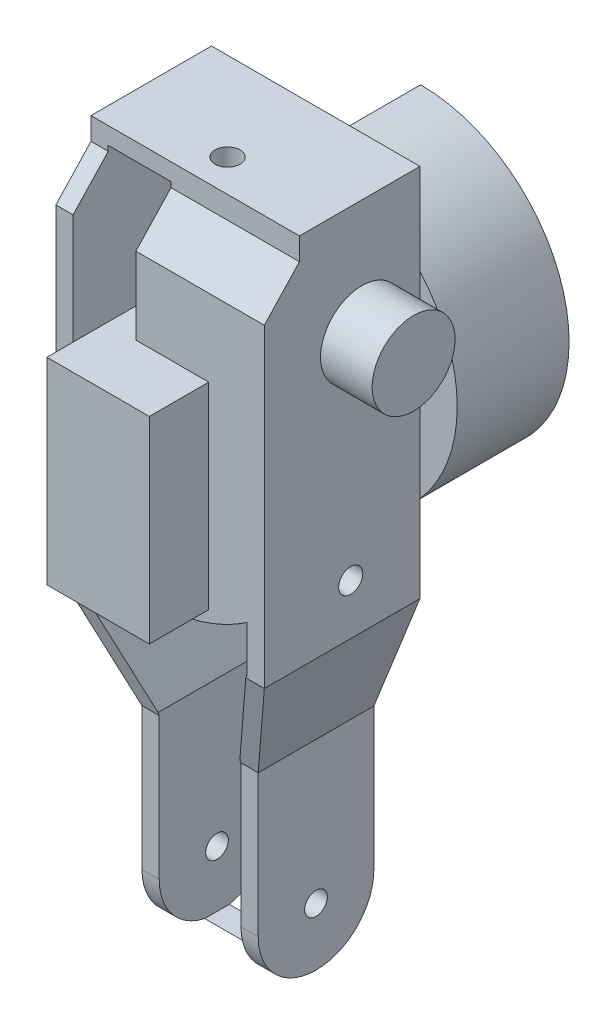
SolidWorks part; units mm, degrees
ref_plane "前视基准面" through (0, 0, 0) normal (0, 0, 1) x (1, 0, 0)
ref_plane "上视基准面" through (0, 0, 0) normal (0, 1, 0) x (1, 0, 0)
ref_plane "右视基准面" through (0, 0, 0) normal (1, 0, 0) x (0, 0, -1)
other "Configuration Table"
sketch "草图1" plane through (0, 0, 0) normal (1, 0, 0) x (0, 0, -1)
  line L0 (-9.04, -3.4) -> (-4.39, -16.885)
  line L1 (-9.04, -40.1) -> (9.04, -40.1)
  line L2 (-9.04, -40.1) -> (-9.04, 40.1)
  line L3 (-9.04, 40.1) -> (9.04, 40.1)
  line L4 (9.04, -40.1) -> (9.04, 40.1)
  line L5 (-9.04, -40.1) -> (9.04, 40.1) construction
  line L6 (-9.04, 40.1) -> (9.04, -40.1) construction
  line L7 (9.04, -33.385) -> (-4.39, -33.385)
  line L8 (9.04, -33.385) -> (9.04, -16.885)
  line L9 (9.04, -16.885) -> (-4.39, -16.885)
  line L10 (-4.39, -33.385) -> (-4.39, -16.885)
  line L11 (-9.04, 40.1) -> (9.04, 40.1)
  line L12 (-9.04, 40.1) -> (-9.04, -3.4)
  line L13 (-9.04, -3.4) -> (9.04, -3.4)
  line L14 (9.04, 40.1) -> (9.04, -3.4)
  line L15 (-4.96, 37.5) -> (-9.04, 33.15)
  line L16 (9.04, 40.1) -> (-4.96, 40.1)
  line L17 (9.04, 40.1) -> (9.04, 37.5)
  line L18 (9.04, 37.5) -> (-4.96, 37.5)
  line L19 (-4.96, 40.1) -> (-4.96, 37.5)
  line L20 (-4.96, 37.5) -> (-9.04, 37.5)
  line L21 (-4.96, 37.5) -> (-4.96, 33.15)
  line L22 (-4.96, 33.15) -> (-9.04, 33.15)
  line L23 (-9.04, 37.5) -> (-9.04, 33.15)
  circle A0 centre (2.325, -33.385) radius 6.715
  point P0 (0, 0)
  dimension "D1" = 18.08
  dimension "D2" = 80.2
  dimension "D3" = 13.43
  dimension "D4" = 16.5
  dimension "D5" = 43.5
  dimension "D6" = 14
  dimension "D7" = 2.6
  dimension "D8" = 4.35
extrude "凸台-拉伸1" add sketch "草图1" along normal blind 24.22 contours L11 L19 L18 L14 | L21 L22 L2 L13 L4 L18 | L22 L21 L15 | L13 L0 L9 L4 | A0 L4 L9 L10 | L7 A0 | L7 A0 region at (0, -9.8108, -1.1053) region at (0, 16.6006, -0.1721) region at (0, -22.5981, -2.325) region at (0, 34.6, 6.32) region at (0, -30.5351, -2.325) region at (0, -36.2349, -2.325) region at (0, 38.8, -2.04)
sketch "草图2" plane through (24.22, 0, 0) normal (1, 0, 0) x (0, 0, -1)
  line L0 (9.04, -16.885) -> (-4.39, -16.885) construction
  line L1 (9.04, -16.885) -> (-4.39, -16.885)
  line L7 (9.04, 40.1) -> (-4.96, 40.1)
  line L8 (-4.96, 40.1) -> (-4.96, 37.5)
  line L9 (-4.96, 37.5) -> (-9.04, 33.15)
  line L10 (-9.04, 33.15) -> (-9.04, -3.4)
  line L11 (-9.04, -3.4) -> (-4.39, -16.885)
  line L12 (-4.39, -16.885) -> (-4.39, -33.385)
  line L13 (9.04, -33.385) -> (9.04, 40.1)
  line L14 (9.04, 40.1) -> (-4.96, 40.1)
  line L15 (-4.96, 40.1) -> (-4.96, 37.5)
  line L16 (-4.96, 37.5) -> (-9.04, 33.15)
  line L17 (-9.04, 33.15) -> (-9.04, -3.4)
  line L18 (-9.04, -3.4) -> (-4.39, -16.885)
  line L19 (-4.39, -16.885) -> (-4.39, -33.385)
  line L20 (9.04, -33.385) -> (9.04, 40.1)
  arc A1 (-4.39, -33.385) -> (9.04, -33.385) centre (2.325, -33.385) ccw
  arc A2 (-4.39, -33.385) -> (9.04, -33.385) centre (2.325, -33.385) ccw
  line M14 (-4.39, -16.885) -> (-4.39, -33.385)
  arc M15 (-4.39, -33.385) -> (9.04, -33.385) centre (2.325, -33.385) ccw
  line M16 (9.04, -33.385) -> (9.04, 40.1)
  dimension "D1" = 0
extrude "切除-拉伸1" cut sketch "草图2" against normal blind 5.36 contours L1 M16 M14 M15 region at (24.22, -27.8236, -2.325)
sketch "草图3" plane through (0, 0, 0) normal (-1, 0, 0) x (0, 0, 1)
  line L0 (-9.04, -16.885) -> (4.39, -16.885) construction
  line L1 (-9.04, -16.885) -> (4.39, -16.885)
  line L7 (4.96, 40.1) -> (-9.04, 40.1)
  line L8 (-9.04, 40.1) -> (-9.04, -33.385)
  line L9 (4.39, -33.385) -> (4.39, -16.885)
  line L10 (4.39, -16.885) -> (9.04, -3.4)
  line L11 (9.04, -3.4) -> (9.04, 33.15)
  line L12 (9.04, 33.15) -> (4.96, 37.5)
  line L13 (4.96, 37.5) -> (4.96, 40.1)
  line L14 (4.96, 40.1) -> (-9.04, 40.1)
  line L15 (-9.04, 40.1) -> (-9.04, -33.385)
  line L16 (4.39, -33.385) -> (4.39, -16.885)
  line L17 (4.39, -16.885) -> (9.04, -3.4)
  line L18 (9.04, -3.4) -> (9.04, 33.15)
  line L19 (9.04, 33.15) -> (4.96, 37.5)
  line L20 (4.96, 37.5) -> (4.96, 40.1)
  arc A1 (-9.04, -33.385) -> (4.39, -33.385) centre (-2.325, -33.385) ccw
  arc A2 (-9.04, -33.385) -> (4.39, -33.385) centre (-2.325, -33.385) ccw
  line M10 (-9.04, 40.1) -> (-9.04, -33.385)
  arc M11 (-9.04, -33.385) -> (4.39, -33.385) centre (-2.325, -33.385) ccw
  line M12 (4.39, -33.385) -> (4.39, -16.885)
  dimension "D1" = 0
extrude "切除-拉伸2" cut sketch "草图3" against normal blind 5.36 contours L1 M10 M11 M12 region at (0, -27.8236, -2.325)
sketch "草图4" plane through (0, 0, -9.04) normal (0, 0, -1) x (-1, 0, 0)
  line L0 (0, -3.4) -> (-5.36, -16.885)
  line L1 (0, -3.4) -> (-24.22, -3.4)
  line L2 (-24.22, -3.4) -> (-18.86, -16.885)
  line L8 (-5.36, -16.885) -> (0, -16.885)
  line L9 (0, -16.885) -> (0, 40.1)
  line L10 (0, 40.1) -> (-24.22, 40.1)
  line L11 (-24.22, 40.1) -> (-24.22, -16.885)
  line L12 (-24.22, -16.885) -> (-18.86, -16.885)
  line L13 (-18.86, -16.885) -> (-18.86, -33.385)
  line L14 (-18.86, -33.385) -> (-5.36, -33.385)
  line L15 (-5.36, -33.385) -> (-5.36, -16.885)
  line L16 (-5.36, -16.885) -> (0, -16.885)
  line L17 (0, -16.885) -> (0, 40.1)
  line L18 (0, 40.1) -> (-24.22, 40.1)
  line L19 (-24.22, 40.1) -> (-24.22, -16.885)
  line L20 (-24.22, -16.885) -> (-18.86, -16.885)
  line L21 (-18.86, -16.885) -> (-18.86, -33.385)
  line L22 (-18.86, -33.385) -> (-5.36, -33.385)
  line L23 (-5.36, -33.385) -> (-5.36, -16.885)
  line M9 (-5.36, -16.885) -> (0, -16.885)
  line M10 (0, -16.885) -> (0, 40.1)
  line M12 (-24.22, 40.1) -> (-24.22, -16.885)
  line M13 (-24.22, -16.885) -> (-18.86, -16.885)
  dimension "D1" = 0
extrude "切除-拉伸3" cut sketch "草图4" against normal through all contours L2 M12 M13 | L0 M10 M9 region at (1.7867, -12.39, -9.04) region at (22.4333, -12.39, -9.04)
sketch "草图6" plane through (24.22, 0, 0) normal (1, 0, 0) x (0, 0, -1)
  line L0 (2.305, 31.47) -> (2.305, 40.1)
  line L1 (-9.04, 40.1) -> (9.04, 40.1) construction
  line L2 (-2.51, 26.655) -> (-9.04, 26.655)
  line L3 (-9.04, -40.1) -> (-9.04, 40.1) construction
  circle A0 centre (2.305, 26.655) radius 4.815
  line M6 (9.04, 40.1) -> (-4.96, 40.1)
  dimension "D3" = 9.63
  dimension "D1" = 6.53
  dimension "D2" = 8.63
extrude "凸台-拉伸3" add sketch "草图6" along normal blind 6 contours A0 M6 region at (24.22, 26.655, -2.305)
sketch "草图8" plane through (0, 0, -9.04) normal (0, 0, -1) x (-1, 0, 0)
  line L0 (-11.3, 18.1) -> (-11.3, 40.1)
  line L1 (-11.3, 18.1) -> (0, 18.1)
  line L2 (-11.3, 35.35) -> (-11.3, 0.85)
  line L8 (-24.22, -3.4) -> (-18.86, -16.885)
  line L9 (-18.86, -16.885) -> (-18.86, -33.385)
  line L10 (-18.86, -33.385) -> (-5.36, -33.385)
  line L11 (-5.36, -33.385) -> (-5.36, -16.885)
  line L12 (-5.36, -16.885) -> (0, -3.4)
  line L13 (0, -3.4) -> (0, 40.1)
  line L14 (0, 40.1) -> (-24.22, 40.1)
  line L15 (-24.22, 40.1) -> (-24.22, -3.4)
  line L16 (-24.22, -3.4) -> (-18.86, -16.885)
  line L17 (-18.86, -16.885) -> (-18.86, -33.385)
  line L18 (-18.86, -33.385) -> (-5.36, -33.385)
  line L19 (-5.36, -33.385) -> (-5.36, -16.885)
  line L20 (-5.36, -16.885) -> (0, -3.4)
  line L21 (0, -3.4) -> (0, 40.1)
  line L22 (0, 40.1) -> (-24.22, 40.1)
  line L23 (-24.22, 40.1) -> (-24.22, -3.4)
  circle A0 centre (-11.3, 18.1) radius 17.25
  dimension "D2" = 34.5
  dimension "D3" = 22
  dimension "D4" = 11.3
  dimension "D1" = 0
extrude "凸台-拉伸4" add sketch "草图8" along normal blind 13 contours L0 A0 L23 L2 | L23 A0 region at (17.373, 18.1, -9.04) region at (25.9721, 18.1, -9.04)
sketch "草图10" plane through (0, 0, 9.04) normal (0, 0, 1) x (1, 0, 0)
  line L0 (5.86, 24.2) -> (5.86, 40.1)
  line L1 (5.86, 24.2) -> (17.76, 24.2)
  line L2 (5.86, 24.2) -> (5.86, 1.3)
  line L3 (5.86, 1.3) -> (17.76, 1.3)
  line L4 (0, 33.15) -> (0, -3.4)
  line L5 (0, -3.4) -> (24.22, -3.4)
  line L6 (24.22, -3.4) -> (24.22, 33.15)
  line L7 (24.22, 33.15) -> (0, 33.15)
  line L8 (0, 33.15) -> (0, -3.4)
  line L9 (0, -3.4) -> (24.22, -3.4)
  line L10 (24.22, -3.4) -> (24.22, 33.15)
  line L11 (24.22, 33.15) -> (0, 33.15)
  line L12 (17.76, 24.2) -> (17.76, 1.3)
  line L13 (5.86, 24.2) -> (0, 24.2)
  line L18 (0, 37.5) -> (0, 33.15)
  line L19 (0, 33.15) -> (24.22, 33.15)
  line L20 (24.22, 33.15) -> (24.22, 37.5)
  line L21 (24.22, 37.5) -> (0, 37.5)
  line L22 (0, 37.5) -> (0, 33.15)
  line L23 (0, 33.15) -> (24.22, 33.15)
  line L24 (24.22, 33.15) -> (24.22, 37.5)
  line L25 (24.22, 37.5) -> (0, 37.5)
  line L26 (0, 40.1) -> (0, 37.5)
  line L27 (0, 37.5) -> (24.22, 37.5)
  line L28 (24.22, 37.5) -> (24.22, 40.1)
  line L29 (24.22, 40.1) -> (0, 40.1)
  line L30 (0, 40.1) -> (0, 37.5)
  line L31 (0, 37.5) -> (24.22, 37.5)
  line L32 (24.22, 37.5) -> (24.22, 40.1)
  line L33 (24.22, 40.1) -> (0, 40.1)
  dimension "D2" = 11.9
  dimension "D3" = 22.9
  dimension "D4" = 15.9
  dimension "D5" = 5.86
  dimension "D1" = 0
  dimension "D6" = 0
  dimension "D7" = 0
extrude "凸台-拉伸5" add sketch "草图10" along normal blind 6.9 contours L12 L1 L2 L3 region at (11.81, 12.75, 9.04)
sketch "草图11" plane through (0, 0, -9.04) normal (0, 0, -1) x (-1, 0, 0)
  line L4 (-22.22, -3.0171) -> (-16.86, -16.5021)
  line L5 (-16.86, -16.5021) -> (-16.86, -31.385)
  line L6 (-16.86, -31.385) -> (-7.36, -31.385)
  line L7 (-7.36, -31.385) -> (-7.36, -16.5021)
  line L8 (-7.36, -16.5021) -> (-2, -3.0171)
  line L9 (-2, -3.0171) -> (-2, 38.1)
  line L10 (-24.22, 6.6704) -> (-24.22, -3.4)
  line L11 (-24.22, -3.4) -> (-18.86, -16.885)
  line L12 (-18.86, -16.885) -> (-18.86, -33.385)
  line L13 (-18.86, -33.385) -> (-5.36, -33.385)
  line L14 (-5.36, -33.385) -> (-5.36, -16.885)
  line L15 (-5.36, -16.885) -> (0, -3.4)
  line L16 (0, -3.4) -> (0, 40.1)
  line L17 (0, 40.1) -> (-24.22, 40.1)
  line L18 (-24.22, 40.1) -> (-24.22, 29.5296)
  line L19 (-11.3, 35.35) -> (-11.3, 0.85)
  line L20 (-24.22, 6.6704) -> (-24.22, -3.4)
  line L21 (-24.22, -3.4) -> (-18.86, -16.885)
  line L22 (-18.86, -16.885) -> (-18.86, -33.385)
  line L23 (-18.86, -33.385) -> (-5.36, -33.385)
  line L24 (-5.36, -33.385) -> (-5.36, -16.885)
  line L25 (-5.36, -16.885) -> (0, -3.4)
  line L26 (0, -3.4) -> (0, 40.1)
  line L27 (0, 40.1) -> (-24.22, 40.1)
  line L28 (-24.22, 40.1) -> (-24.22, 29.5296)
  line L29 (-11.3, 35.35) -> (-11.3, 0.85)
  line L30 (-2, 38.1) -> (-22.22, 38.1)
  line L31 (-22.22, 38.1) -> (-22.22, 33.953)
  line L32 (-9.3, 37.2458) -> (-9.3, -1.0458)
  line L33 (-22.22, 2.247) -> (-22.22, -3.0171)
  line L34 (-22.22, 33.953) -> (-22.22, 31.4535)
  line L35 (-22.22, 2.247) -> (-22.22, 4.7465)
  line L36 (-16.86, -31.385) -> (-16.86, -39.9462)
  line L37 (-16.86, -39.9462) -> (-7.36, -39.9462)
  line L38 (-7.36, -39.9462) -> (-7.36, -31.385)
  line L39 (-9.3, 37.2458) -> (-9.3, 38.1)
  line L44 (-17.76, 24.2) -> (-17.76, 1.3)
  line L45 (-5.86, 24.2) -> (-17.76, 24.2)
  line L46 (-5.86, 1.3) -> (-5.86, 24.2)
  line L47 (-17.76, 1.3) -> (-5.86, 1.3)
  line L48 (-17.76, 24.2) -> (-17.76, 1.3)
  line L49 (-5.86, 24.2) -> (-17.76, 24.2)
  line L50 (-5.86, 1.3) -> (-5.86, 24.2)
  line L51 (-17.76, 1.3) -> (-5.86, 1.3)
  arc A0 (-9.3, 37.2458) -> (-22.22, 33.953) centre (-11.3, 18.1) ccw
  arc A1 (-22.22, 2.247) -> (-9.3, -1.0458) centre (-11.3, 18.1) ccw
  arc A2 (-24.22, 6.6704) -> (-11.3, 0.85) centre (-11.3, 18.1) ccw
  arc A3 (-11.3, 35.35) -> (-24.22, 29.5296) centre (-11.3, 18.1) ccw
  arc A4 (-24.22, 6.6704) -> (-11.3, 0.85) centre (-11.3, 18.1) ccw
  arc A5 (-11.3, 35.35) -> (-24.22, 29.5296) centre (-11.3, 18.1) ccw
  dimension "D1" = 0
  dimension "D2" = 2
  dimension "D3" = 0
extrude "切除-拉伸4" cut sketch "草图11" against normal through all contours A1 L33 L4 L5 L6 L7 L8 L9 L30 L39 L32 | L23 L38 L6 L36 | L37 L38 L23 L36 region at (9.7639, -1.6186, -9.04) region at (12.11, -32.385, -9.04) region at (12.11, -36.6656, -9.04)
sketch "草图12" plane through (18.86, 0, 0) normal (1, 0, 0) x (0, 0, -1)
  line L3 (9.04, -33.385) -> (9.04, -16.885)
  line L4 (9.04, -16.885) -> (-4.39, -16.885)
  line L5 (-4.39, -16.885) -> (-4.39, -33.385)
  line L6 (9.04, -33.385) -> (9.04, -16.885)
  line L7 (9.04, -16.885) -> (-4.39, -16.885)
  line L8 (-4.39, -16.885) -> (-4.39, -33.385)
  circle A0 centre (2.325, -33.385) radius 1.315
  arc A1 (-4.39, -33.385) -> (9.04, -33.385) centre (2.325, -33.385) ccw
  arc A2 (-4.39, -33.385) -> (9.04, -33.385) centre (2.325, -33.385) ccw
  point P6 (0, 0)
  dimension "D2" = 2.63
  dimension "D1" = 0
extrude "切除-拉伸5" cut sketch "草图12" against normal through all contours A0
sketch "草图13" plane through (0, 0, 0) normal (-1, 0, 0) x (0, 0, 1)
  line L0 (-4.04, 2.46) -> (-9.04, 2.46)
  line L1 (-1, 5.5) -> (-1, 40.1)
  line L6 (-9.04, 40.1) -> (-9.04, -3.4)
  line L7 (-9.04, -3.4) -> (9.04, -3.4)
  line L8 (9.04, -3.4) -> (9.04, 33.15)
  line L9 (9.04, 33.15) -> (4.96, 37.5)
  line L10 (4.96, 37.5) -> (4.96, 40.1)
  line L11 (4.96, 40.1) -> (-9.04, 40.1)
  line L12 (-9.04, 40.1) -> (-9.04, -3.4)
  line L13 (-9.04, -3.4) -> (9.04, -3.4)
  line L14 (9.04, -3.4) -> (9.04, 33.15)
  line L15 (9.04, 33.15) -> (4.96, 37.5)
  line L16 (4.96, 37.5) -> (4.96, 40.1)
  line L17 (4.96, 40.1) -> (-9.04, 40.1)
  circle A0 centre (-1, 2.46) radius 3.04
  circle A1 centre (-1, 2.46) radius 1.4
  dimension "D3" = 6.08
  dimension "D5" = 2.8
  dimension "D2" = 5
  dimension "D4" = 34.6
  dimension "D1" = 0
extrude "切除-拉伸6" cut sketch "草图13" against normal through all contours A1 region at (0, 2.46, -1)
sketch "草图14" plane through (0, 40.1, 0) normal (0, 1, 0) x (1, 0, 0)
  line L0 (12.11, 1.84) -> (12.11, 9.04)
  line L1 (9.07, -1.2) -> (0, -1.2)
  line L2 (15.15, -1.2) -> (24.22, -1.2)
  line L4 (0, 9.04) -> (0, -4.96)
  line L5 (0, -4.96) -> (24.22, -4.96)
  line L6 (24.22, -4.96) -> (24.22, 9.04)
  line L7 (24.22, 9.04) -> (0, 9.04)
  line L8 (0, 9.04) -> (0, -4.96)
  line L9 (0, -4.96) -> (24.22, -4.96)
  line L10 (24.22, -4.96) -> (24.22, 9.04)
  line L11 (24.22, 9.04) -> (0, 9.04)
  circle A0 centre (12.11, -1.2) radius 3.04
  circle A1 centre (12.11, -1.2) radius 1.45
  dimension "D2" = 6.08
  dimension "D4" = 2.9
  dimension "D3" = 7.2
  dimension "D1" = 0
extrude "切除-拉伸7" cut sketch "草图14" against normal up to surface (15.9 mm away) contours A1 region at (12.11, 40.1, 1.2) up to face at (10.9733, 24.2, 5.3133)
sketch "草图15" plane through (0, 0, -22.04) normal (0, 0, -1) x (-1, 0, 0)
  line L1 (-11.3, 0.85) -> (-11.3, 35.35)
  line L2 (-11.3, 0.85) -> (-11.3, 35.35)
  circle A0 centre (-11.3, 18.1) radius 3.61
  arc A1 (-11.3, 35.35) -> (-11.3, 0.85) centre (-11.3, 18.1) ccw
  arc A2 (-11.3, 35.35) -> (-11.3, 0.85) centre (-11.3, 18.1) ccw
  dimension "D2" = 7.22
  dimension "D1" = 0
extrude "凸台-拉伸6" add sketch "草图15" against normal up to surface (13 mm away) contours L2 A0 region at (9.7679, 18.1, -22.04) up to face at (12.1256, 2.5653, -9.04)
